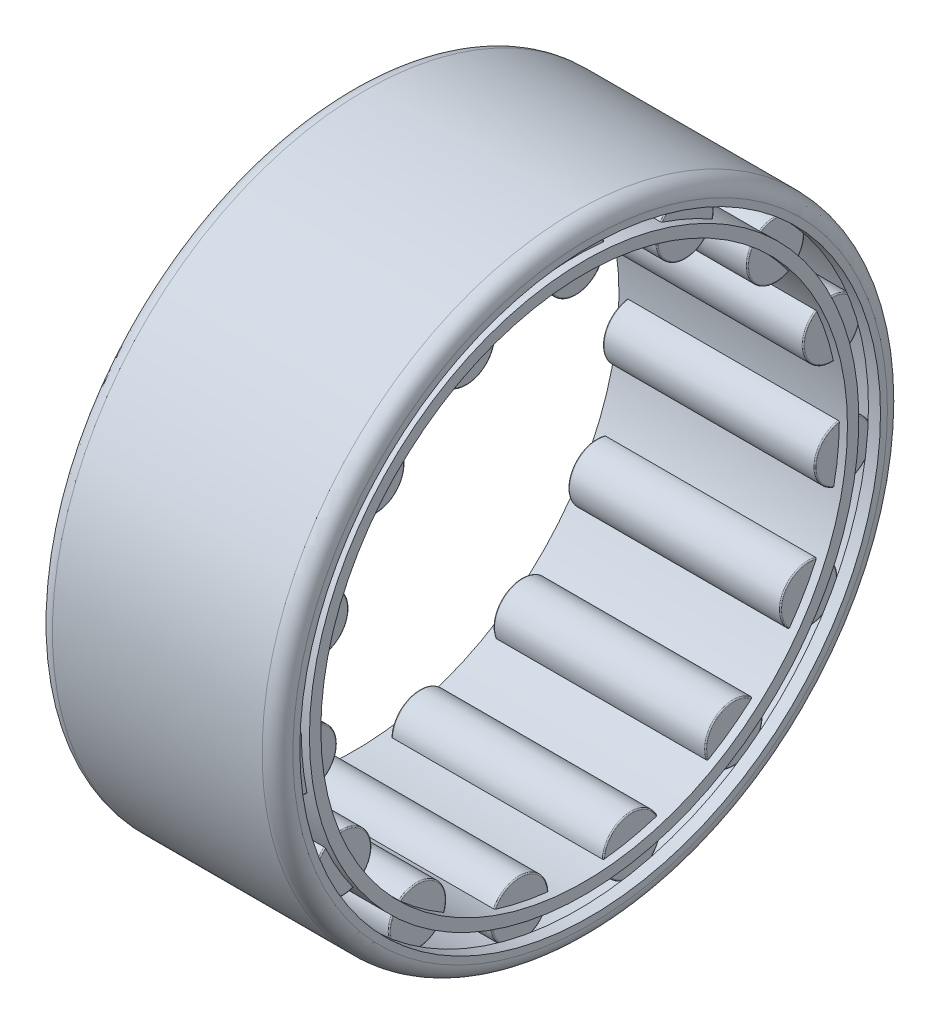
SolidWorks part; units mm, degrees
ref_plane "Plane1" through (0, 0, 0) normal (0, 0, 1) x (1, 0, 0)
ref_plane "Plane2" through (0, 0, 0) normal (0, 1, 0) x (1, 0, 0)
ref_plane "Plane3" through (0, 0, 0) normal (1, 0, 0) x (0, 0, -1)
sketch "Clipboard" plane through (0, 0, 0) normal (0, 0, 1) x (1, 0, 0)
  line L0 (-10, 0) -> (10, 0) construction
  line L1 (41.1529, 1.4371) -> (62.7517, -4.3503)
  line L2 (41.1529, 1.4371) -> (75.4583, 10.6292)
  line L3 (41.1529, 1.4371) -> (62.7517, -4.3503)
  line L4 (41.1529, 1.4371) -> (-22.3471, -0.7804)
  dimension "BallCLRad" = 35.5155
  dimension "Bore" = 63.5
sketch "InnRacSke" plane through (0, 0, 0) normal (0, 0, 1) x (1, 0, 0)
  line L0 (-14.2875, 38.3286) -> (-15.875, 38.3286)
  line L1 (-15.875, 38.3286) -> (-15.875, 39.243)
  line L2 (-13.843, 41.275) -> (13.843, 41.275)
  line L4 (15.875, 39.243) -> (15.875, 38.3286)
  line L5 (15.875, 38.3286) -> (14.2875, 38.3286)
  line L6 (14.2875, 38.3286) -> (14.2875, 39.2811)
  line L7 (14.2875, 39.2811) -> (-14.2875, 39.2811)
  line L8 (-14.2875, 39.2811) -> (-14.2875, 38.3286)
  line L9 (-31.75, 0) -> (31.75, 0) construction
  arc A0 (-15.875, 39.243) -> (-13.843, 41.275) centre (-13.843, 39.243) cw
  arc A2 (13.843, 41.275) -> (15.875, 39.243) centre (13.843, 39.243) cw
  dimension "D1" = 78.5622
revolve "Race" add sketch "InnRacSke" angle 360 about L9 reverse direction yes
sketch "RolDetSke" plane through (0, 0, 0) normal (0, 0, 1) x (1, 0, 0)
  line L0 (-14.0018, 39.131) -> (-14.0017, 35.5155)
  line L1 (-14.0017, 35.5155) -> (14.0017, 35.5155)
  line L2 (14.0017, 35.5155) -> (14.0018, 39.131)
  line L3 (13.8511, 39.2816) -> (-13.8511, 39.2816)
  line L4 (-28.575, 35.5155) -> (28.575, 35.5155) construction
  arc A0 (14.0018, 39.131) -> (13.8511, 39.2816) centre (13.8511, 39.131) ccw
  arc A1 (-13.8511, 39.2816) -> (-14.0018, 39.131) centre (-13.8511, 39.131) ccw
  dimension "Roller_length" = 28.0035
  dimension "Roller_diameter" = 7.5321
revolve "RollerDetailed" add sketch "RolDetSke" angle 360 about L4 reverse direction yes
ref_axis "Axis1" through (-50, 0, 0) along (1, 0, 0)
sketch "CagSpiSke" plane through (0, 0, 0) normal (0, 0, 1) x (1, 0, 0)
  line L0 (15.0812, 34.7623) -> (15.0812, 36.2688)
  line L1 (15.0812, 36.2688) -> (-15.0813, 36.2688)
  line L2 (-15.0813, 36.2688) -> (-15.0813, 34.7623)
  line L3 (-15.0813, 34.7623) -> (15.0812, 34.7623)
  line L4 (-31.75, 0) -> (31.75, 0) construction
  dimension "D2" = 69.5247
  dimension "halfWidth" = 15.0813
revolve "CageSpine" add sketch "CagSpiSke" angle 360 about L4
pattern_circular "RollersDetailed" count 15 every 24 about axis through (-50, 0, 0) along (1, 0, 0) of "RollerDetailed"
sketch "RolSimSke" plane through (0, 0, 0) normal (0, 0, 1) x (1, 0, 0)
  line L0 (-25.4, 0) -> (25.4, 0) construction
  line L2 (-13.8511, 39.2821) -> (13.8511, 39.2821)
  line L3 (-14.0018, 39.1315) -> (-14.0018, 31.9006)
  line L4 (-13.8511, 31.75) -> (13.8511, 31.75)
  line L5 (14.0017, 39.1315) -> (14.0017, 31.9006)
  arc A0 (-14.0018, 31.9006) -> (-13.8511, 31.75) centre (-13.8511, 31.9006) ccw
  arc A1 (-13.8511, 39.2821) -> (-14.0018, 39.1315) centre (-13.8511, 39.1315) ccw
  arc A2 (14.0017, 39.1315) -> (13.8511, 39.2821) centre (13.8511, 39.1315) ccw
  arc A3 (13.8511, 31.75) -> (14.0017, 31.9006) centre (13.8511, 31.9006) ccw
  point P10 (-14.0018, 31.75)
  point P15 (14.0017, 39.2821)
  point P18 (14.0017, 31.75)
  dimension "Bore" = 63.5
  dimension "D1" = 0.1506
  dimension "Roller_length" = 28.0035
  dimension "Roller_diameter" = 7.5321
  dimension "halfWidth" = 14.0017
revolve "RollersSimplified" [suppressed] add sketch "RolSimSke" angle 360 about L0
equation "\"BallCLRad@Clipboard\" =  ( \"D1@InnRacSke\" + \"Bore@Clipboard\" )  / 4"
equation "\"RollerCLRad@RolDetSke\" = \"BallCLRad@Clipboard\""
equation "\"halfCyl@InnRacSke\" = \"Cyl_Len@InnRacSke\" / 2"
equation "\"Roller_diameter@RolDetSke\" =  ( \"D1@InnRacSke\" - \"Bore@Clipboard\" )  / 2 + .001"
equation "\"Roller_radius@RolDetSke\" = \"Roller_diameter@RolDetSke\" / 50"
equation "\"Roller_length@RolDetSke\" = \"Cyl_Len@InnRacSke\" * .98"
equation "\"halfLength@RolDetSke\" = \"Roller_length@RolDetSke\" / 2"
equation "\"Cage_width@CagSpiSke\" =  ( \"Cyl_Len@InnRacSke\" + \"Width@InnRacSke\" )  / 2"
equation "\"halfWidth@CagSpiSke\" = \"Cage_width@CagSpiSke\" / 2"
equation "\"Roller_length@RolSimSke\" = \"Cyl_Len@InnRacSke\" * .98"
equation "\"halfWidth@RolSimSke\" = \"Roller_length@RolSimSke\" / 2"
equation "\"D1@RolSimSke\" = \"Roller_radius@RolDetSke\""
equation "\"Roller_diameter@RolSimSke\" =  ( \"D1@InnRacSke\" - \"Bore@Clipboard\" )  / 2 + .001"
equation "\"Cage_thickness@CagSpiSke\"  = \"Roller_diameter@RolDetSke\" / 5"
equation "\"D2@CagSpiSke\" =  \"RollerCLRad@RolDetSke\" * 2 - \"Cage_thickness@CagSpiSke\""
equation "\"Max_count@Clipboard\" = int( 3.14159265 / atn(( \"Roller_diameter@RolDetSke\" / 2) / sqr( \"RollerCLRad@RolDetSke\"  *  \"RollerCLRad@RolDetSke\" - ( \"Roller_diameter@RolDetSke\" / 2) *  ( \"Roller_diameter@RolDetSke\" / 2))))"
equation "\"Max_count@Clipboard\" = ((sgn( \"Max_count@Clipboard\" - \"Count@Clipboard\" )-1)*( \"Max_count@Clipboard\" - \"Count@Clipboard\" ))/-2+ \"Count@Clipboard\""
equation "\"Count@RollersDetailed\" = int( \"Show_count@Clipboard\" ) "
equation "\"Count@RollersDetailed\" = ((sgn( \"Count@RollersDetailed\" - \"Max_count@Clipboard\" )-1)*( \"Count@RollersDetailed\" - \"Max_count@Clipboard\" ))/-2+ \"Max_count@Clipboard\""
equation "\"Count@RollersDetailed\" = ((sgn( \"Count@RollersDetailed\" - \"Min_count@Clipboard\" )+1)*( \"Count@RollersDetailed\" - \"Min_count@Clipboard\"))/2 +\"Min_count@Clipboard\""
equation "\"Angle@RollersDetailed\" = 360.0 / \"Max_count@Clipboard\""
equation "\"Angle@CageSpine\" =  \"Angle@RollersDetailed\" * ( \"Count@RollersDetailed\" -1 + int( \"Count@RollersDetailed\" / \"Max_count@Clipboard\" ) )  + 0.001 -  int( \"Count@RollersDetailed\" / \"Max_count@Clipboard\" ) * 0.001"
equation "\"Angle@CageSpine\" =  \"Angle@CageSpine\" * int( \"Min_count@Clipboard\" / 2) + int(1 / \"Min_count@Clipboard\")  * 0.001"
equation "\"Bore@RolSimSke\" = \"Bore@Clipboard\""
